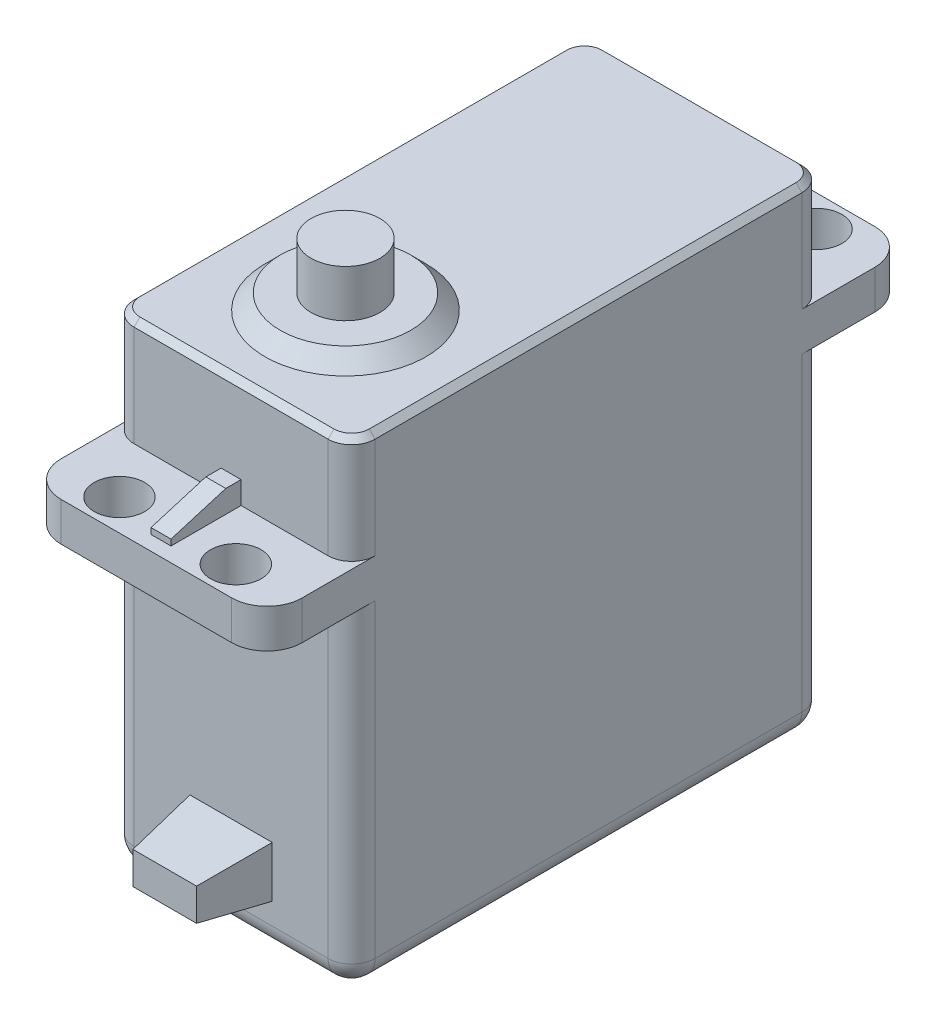
SolidWorks part; units mm, degrees
ref_plane "Front Plane" through (0, 0, 0) normal (0, 0, 1) x (1, 0, 0)
ref_plane "Top Plane" through (0, 0, 0) normal (0, 1, 0) x (1, 0, 0)
ref_plane "Right Plane" through (0, 0, 0) normal (1, 0, 0) x (0, 0, -1)
sketch "Sketch1" plane through (0, 0, 0) normal (1, 0, 0) x (0, 0, -1)
  line L1 (0, 0) -> (40.3, 0)
  line L2 (0, 0) -> (0, 40.75)
  line L3 (0, 40.75) -> (40.3, 40.75)
  line L4 (40.3, 0) -> (40.3, 40.75)
  dimension "D1" = 40.75
  dimension "D2" = 40.3
extrude "Boss-Extrude1" add sketch "Sketch1" along normal mid plane 20.5
sketch "Sketch2" plane through (0, 40.75, 0) normal (0, 1, 0) x (1, 0, 0)
  line L0 (10.25, 0) -> (-10.25, 0) construction
  line L1 (0, -25.3275) -> (0, 25.3275) construction
  circle A0 centre (0, 9.73) radius 2.93
  dimension "D2" = 5.86
  dimension "D1" = 9.73
extrude "Boss-Extrude2" add sketch "Sketch2" along normal blind 5.3
sketch "Sketch3" plane through (0, 40.75, 0) normal (0, 1, 0) x (1, 0, 0)
  circle A1 centre (0, 9.73) radius 2.93 construction
  circle A3 centre (0, 9.73) radius 6.85
  dimension "D1" = 13.7
extrude "Boss-Extrude3" add sketch "Sketch3" along normal blind 1.3
chamfer "Chamfer1" distance 1.3 angle 45 1 edges at (0, 42.05, -2.88)
sketch "Sketch4" plane through (0, 0, 0) normal (0, 1, 0) x (1, 0, 0)
  line L1 (-10.25, 0) -> (10.25, 0)
  line L2 (-10.25, 0) -> (-10.25, -7.2)
  line L3 (-10.25, -7.2) -> (10.25, -7.2)
  line L4 (10.25, 0) -> (10.25, -7.2)
  line L5 (10.25, 40.3) -> (-10.25, 40.3)
  line L6 (10.25, 40.3) -> (10.25, 47.5)
  line L7 (10.25, 47.5) -> (-10.25, 47.5)
  line L8 (-10.25, 40.3) -> (-10.25, 47.5)
  dimension "D1" = 7.2
extrude "Boss-Extrude4" add sketch "Sketch4" along normal blind 3.3 from offset 28.36
ref_plane "Plane1" through (0, 0, -20.15) normal (0, 0, 1) x (1, 0, 0)
sketch "Sketch5" plane through (0, 31.66, 0) normal (0, 1, 0) x (1, 0, 0)
  line L0 (0, -25.3275) -> (0, 25.3275) construction
  line L1 (4.95, -4.545) -> (4.95, 44.845) construction
  line L3 (-11.275, 20.15) -> (11.275, 20.15) construction
  circle A0 centre (4.95, -4.545) radius 2.15
  circle A1 centre (-4.95, -4.545) radius 2.15
  circle A2 centre (4.95, 44.845) radius 2.15
  circle A3 centre (-4.95, 44.845) radius 2.15
  point P8 (4.95, 20.15)
  dimension "D1" = 4.3
  dimension "D2" = 9.9
  dimension "D3" = 49.39
extrude "Cut-Extrude1" cut sketch "Sketch5" against normal up to next
fillet "Fillet1" radius 2 12 edges at (0, 0, 0) (10.25, 0, -20.15) (0, 0, -40.3) (-10.25, 0, -20.15) (-10.25, 36.205, 0) (10.25, 36.205, 0) (-10.25, 36.205, -40.3) (10.25, 36.205, -40.3) (-10.25, 14.18, -40.3) (10.25, 14.18, -40.3) (-10.25, 14.18, 0) (10.25, 14.18, 0)
fillet "Fillet2" radius 3 4 edges at (-10.25, 30.01, -47.5) (10.25, 30.01, -47.5) (10.25, 30.01, 7.2) (-10.25, 30.01, 7.2)
sketch "Sketch7" plane through (0, 0, 0) normal (1, 0, 0) x (0, 0, -1)
  line L0 (0, 31.66) -> (0, 33.57)
  line L1 (0, 31.66) -> (0, 40.75) construction
  line L2 (0, 33.57) -> (-1.3, 33.57)
  line L3 (-1.3, 33.57) -> (-5.96, 32.1696)
  line L4 (-5.96, 32.1696) -> (-5.96, 31.66)
  line L5 (-4.2, 31.66) -> (-7.2, 31.66) construction
  line L6 (-5.96, 31.66) -> (0, 31.66)
  line L7 (-4.2, 28.36) -> (2, 28.36) construction
  dimension "D1" = 1.3
  dimension "D2" = 0.5096
  dimension "D3" = 5.96
  dimension "D4" = 5.21
extrude "Boss-Extrude5" add sketch "Sketch7" along normal mid plane 1.7
mirror "Mirror1" about plane through (0, 0, -20.15) normal (0, 0, 1) of "Boss-Extrude5"
chamfer "Chamfer2" distance 0.5 angle 45 8 edges at (-10.25, 40.75, -20.15) (-9.6642, 40.75, -39.7142) (-9.6642, 40.75, -0.5858) (0, 40.75, -40.3) (0, 40.75, 0) (9.6642, 40.75, -39.7142) (9.6642, 40.75, -0.5858) (10.25, 40.75, -20.15)
sketch "Sketch8" plane through (0, 0, 0) normal (0, 0, 1) x (1, 0, 0)
  line L0 (8.25, 0) -> (-8.25, 0) construction
  line L1 (-3.5, 8.17) -> (3.5, 8.17)
  line L2 (-3.5, 8.17) -> (-3.5, 3.84)
  line L3 (-3.5, 3.84) -> (3.5, 3.84)
  line L4 (3.5, 8.17) -> (3.5, 3.84)
  point P4 (0, 3.84)
  dimension "D1" = 7
  dimension "D2" = 4.33
  dimension "D3" = 3.84
extrude "Boss-Extrude6" add sketch "Sketch8" along normal blind 5.64 draft 8
equation "\"D1@Sketch2\"=6.8+5.86/2"
equation "\"D2@Sketch5\"=5.6+4.3"
equation "\"D3@Sketch5\"=45.09+\"D1@Sketch5\""
